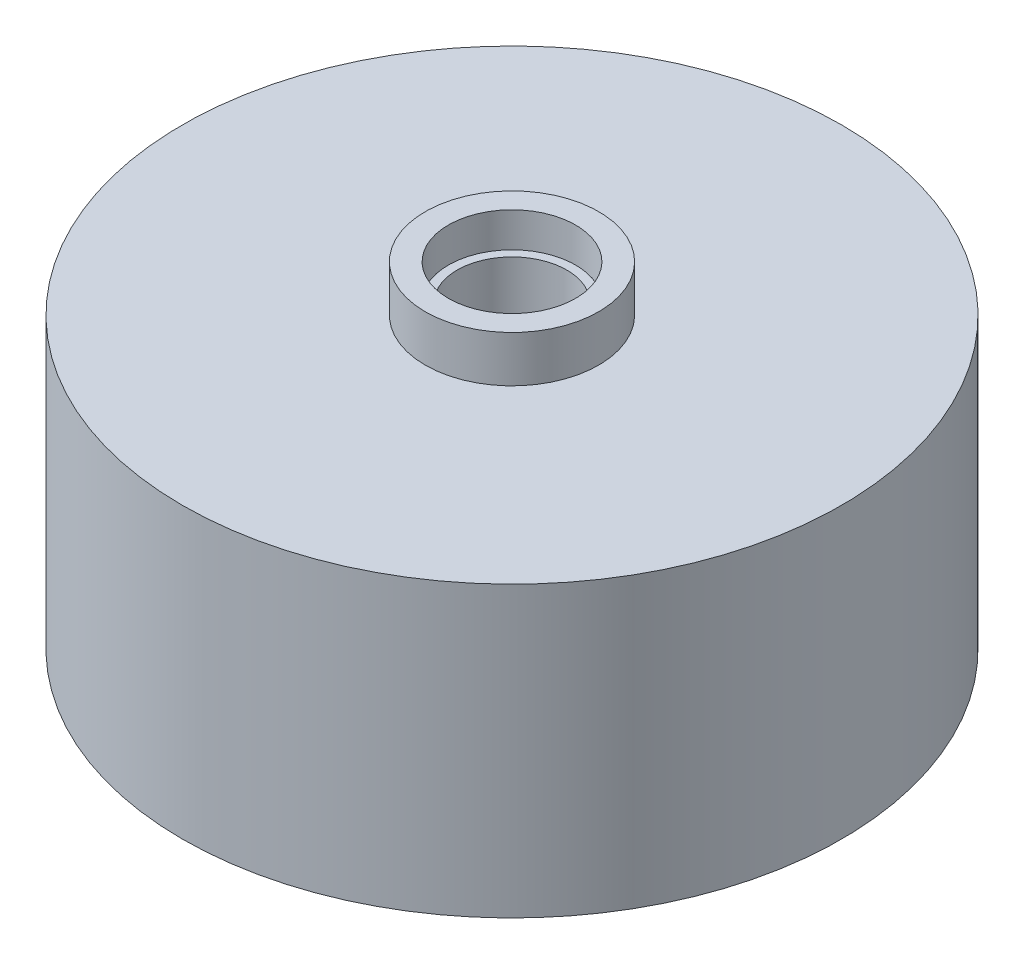
SolidWorks part; units mm, degrees
ref_plane "前视基准面" through (0, 0, 0) normal (0, 0, 1) x (1, 0, 0)
ref_plane "上视基准面" through (0, 0, 0) normal (0, 1, 0) x (1, 0, 0)
ref_plane "右视基准面" through (0, 0, 0) normal (1, 0, 0) x (0, 0, -1)
sketch "草图1" plane through (0, 0, 0) normal (0, 1, 0) x (1, 0, 0)
  circle A0 centre (0, 0) radius 28.5
  circle A1 centre (0, 0) radius 4.75
  dimension "D1" = 57
  dimension "D2" = 9.5
extrude "凸台-拉伸1" add sketch "草图1" along normal blind 12.5 and the other way blind 12.5
sketch "草图2" plane through (0, 12.5, 0) normal (0, 1, 0) x (1, 0, 0)
  circle A0 centre (0, 0) radius 4.75
  circle A1 centre (0, 0) radius 7.5
  dimension "D1" = 9.5
  dimension "D2" = 15
extrude "凸台-拉伸2" add sketch "草图2" along normal blind 4
sketch "草图3" plane through (0, -12.5, 0) normal (0, -1, 0) x (-1, 0, 0)
  circle A0 centre (0, 0) radius 4.75
  circle A1 centre (0, 0) radius 7.5
  dimension "D1" = 15
extrude "凸台-拉伸3" add sketch "草图3" along normal blind 4
sketch "草图4" plane through (0, 16.5, 0) normal (0, 1, 0) x (1, 0, 0)
  circle A0 centre (0, 0) radius 5.5
  dimension "D1" = 11
extrude "切除-拉伸1" cut sketch "草图4" against normal blind 3
sketch "草图5" plane through (0, -16.5, 0) normal (0, -1, 0) x (-1, 0, 0)
  circle A0 centre (0, 0) radius 5.5
  dimension "D1" = 11
extrude "切除-拉伸2" cut sketch "草图5" against normal blind 3
